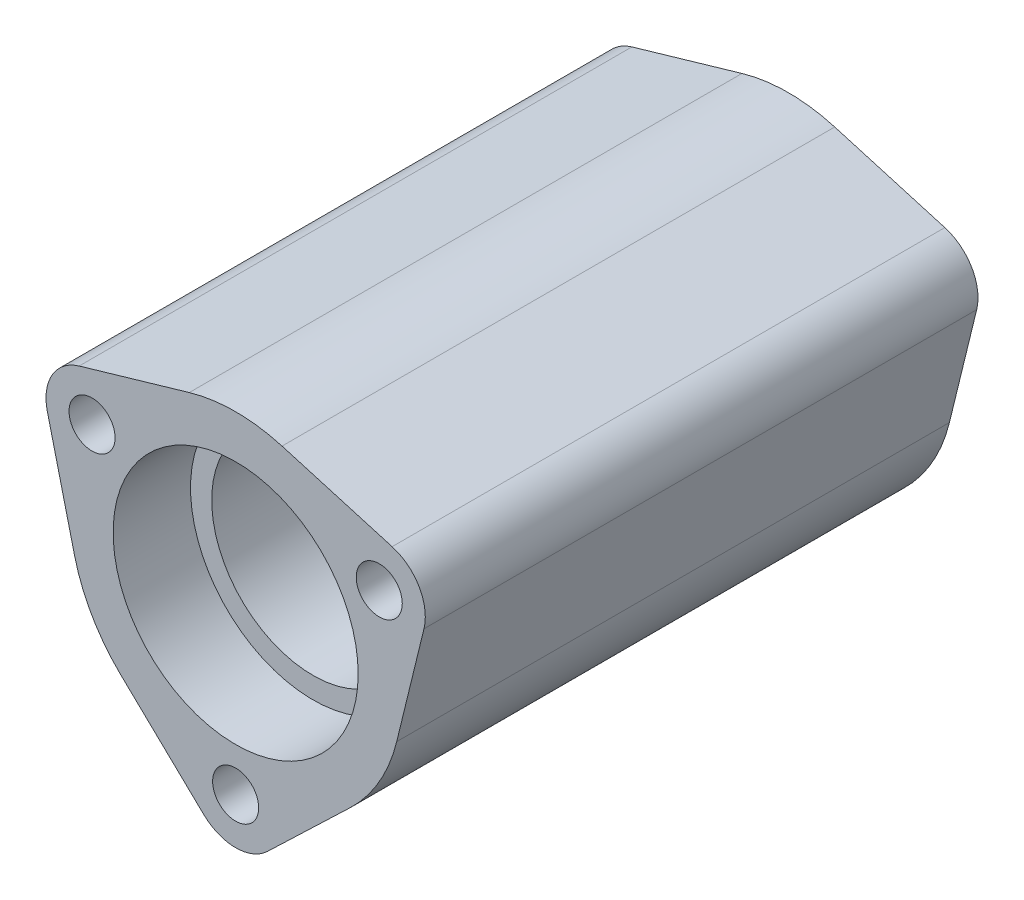
SolidWorks part; units mm, degrees
ref_plane "Спереди" through (0, 0, 0) normal (0, 0, 1) x (1, 0, 0)
ref_plane "Сверху" through (0, 0, 0) normal (0, 1, 0) x (1, 0, 0)
ref_plane "Справа" through (0, 0, 0) normal (1, 0, 0) x (0, 0, -1)
sketch "Эскиз1" plane through (0, 0, 0) normal (0, 0, 1) x (1, 0, 0)
  line L0 (-7.7942, 4.5) -> (0, 0) construction
  line L1 (0, 0) -> (0, -9) construction
  line L2 (-8.4933, 6.9003) -> (-2.5167, 8.641)
  line L3 (1.7292, -10.8056) -> (6.2249, -6.5)
  line L4 (-1.7292, -10.8056) -> (-6.2249, -6.5)
  line L5 (8.4933, 6.9003) -> (2.5167, 8.641)
  line L6 (10.2225, 3.9053) -> (8.7416, -2.141)
  line L7 (0, 0) -> (7.7942, 4.5) construction
  line L8 (-8.7416, -2.141) -> (-10.2225, 3.9053)
  circle A0 centre (0, 0) radius 9 construction
  arc A1 (6.2249, -6.5) -> (8.7416, -2.141) centre (0, 0) ccw
  arc A2 (-8.4933, 6.9003) -> (-10.2225, 3.9053) centre (-7.7942, 4.5) ccw
  arc A3 (-1.7292, -10.8056) -> (1.7292, -10.8056) centre (0, -9) ccw
  arc A4 (10.2225, 3.9053) -> (8.4933, 6.9003) centre (7.7942, 4.5) ccw
  arc A5 (2.5167, 8.641) -> (-2.5167, 8.641) centre (0, 0) ccw
  arc A6 (-8.7416, -2.141) -> (-6.2249, -6.5) centre (0, 0) ccw
  dimension "D2" = 18
  dimension "D3" = 120
  dimension "D4" = 5
  dimension "D5" = 120
extrude "тело" add sketch "Эскиз1" along normal blind 15 and the other way blind 15
sketch "Эскиз2" plane through (0, 0, 15) normal (0, 0, 1) x (1, 0, 0)
  circle A0 centre (0, 0) radius 6.65
  dimension "D1" = 13.3
extrude "углубление под подшипник" cut sketch "Эскиз2" against normal blind 4.2
mirror "Зеркальное отражение1" about plane through (0, 0, 0) normal (0, 0, 1) of "углубление под подшипник"
sketch "Эскиз3" plane through (0, 0, 10.8) normal (0, 0, 1) x (1, 0, 0)
  circle A0 centre (0, 0) radius 5.5
  dimension "D1" = 11
extrude "сквозное отверстие" cut sketch "Эскиз3" against normal through all
sketch "Эскиз4" plane through (0, 0, 15) normal (0, 0, 1) x (1, 0, 0)
  circle A0 centre (-7.7942, 4.5) radius 1.25
  circle A1 centre (0, -9) radius 1.25
  circle A2 centre (7.7942, 4.5) radius 1.25
  dimension "D1" = 2.5
extrude "отверстия для шурупов" cut sketch "Эскиз4" against normal through all
